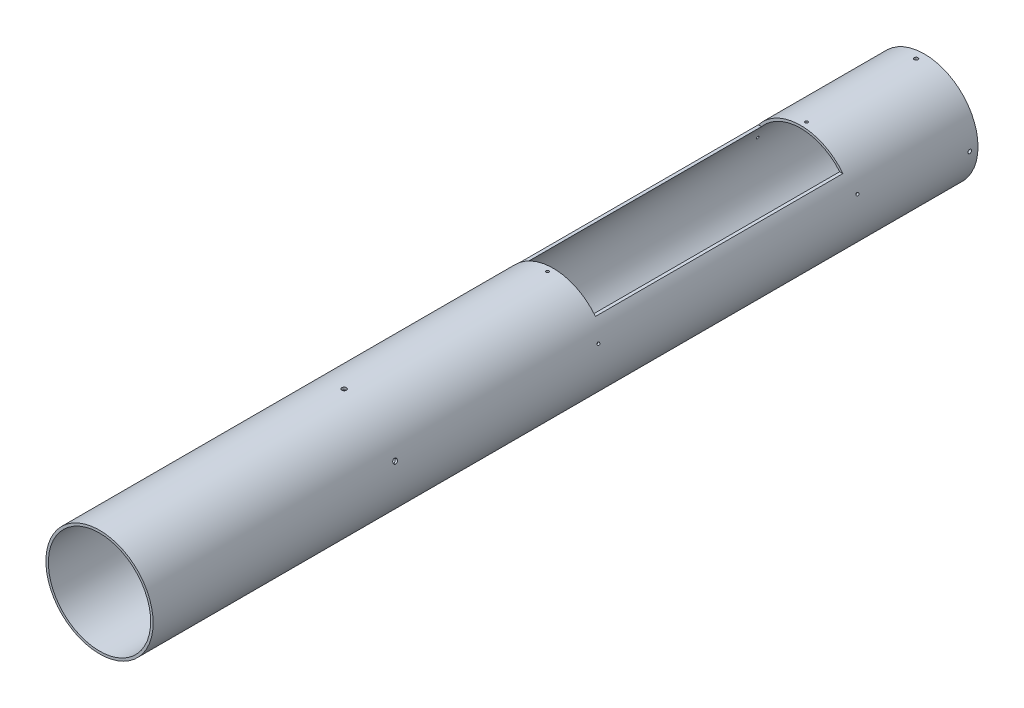
SolidWorks part; units mm, degrees
note: '?' marks a value the reader was unsure of.
material "Thornel Mat VMA"
ref_plane "Front Plane" through (0, 0, 0) normal (0, 0, 1) x (1, 0, 0)
ref_plane "Top Plane" through (0, 0, 0) normal (0, 1, 0) x (1, 0, 0)
ref_plane "Right Plane" through (0, 0, 0) normal (1, 0, 0) x (0, 0, -1)
sketch "Sketch1" plane through (0, 0, 0) normal (0, 0, 1) x (1, 0, 0)
  circle A0 centre (0, 0) radius 62
  circle A1 centre (0, 0) radius 65
  dimension "D1" = 124
  dimension "D2" = 3
extrude "Boss-Extrude1" add sketch "Sketch1" along normal blind 1000
ref_axis "Axis1" through (0, 0, 1000) along (0, 0, -1)?
sketch "Sketch2" plane through (0, 0, 0) normal (0, 1, 0) x (1, 0, 0)
  line L0 (62, 0) -> (-62, 0) construction
  circle A0 centre (0, -224) radius 1
  circle A1 centre (0, -184) radius 1
  dimension "D1" = 2
  dimension "D3" = 2
  dimension "D2" = 224
  dimension "D4" = 40
ref_plane "Plane1" through (0, 0, 0) normal (-0.7071, 0.7071, 0) x (0.7071, 0.7071, 0)
ref_plane "Plane2" through (0, 40, 0) normal (0, 1, 0) x (1, 0, 0)
sketch "Sketch4" plane through (0, 40, 0) normal (0, 1, 0) x (1, 0, 0)
  line L0 (-65, 0) -> (-65, -1000) construction
  line L1 (-65, -150) -> (65, -150)
  line L2 (-65, -150) -> (-65, -450)
  line L3 (-65, -450) -> (65, -450)
  line L4 (65, -150) -> (65, -450)
  line L5 (65, -1000) -> (65, 0) construction
  line L6 (65, 0) -> (-65, 0) construction
  dimension "D1" = 150
  dimension "D2" = 300
extrude "Cut-Extrude4" cut sketch "Sketch4" along normal blind 516
hole_wizard "M4 Clearance Hole2" positions "3DSketch2" profile "Sketch18" hole size "M4" standard "ISO" end condition up to next
sketch3d "3DSketch2"
  line L0 (0, 0, 1000) -> (0, 0, 0) construction
  circle A0 centre (0, 0, 10) radius 65
  circle A2 centre (0, 0, 1000) radius 65 construction
  circle A3 centre (0, 0, 0) radius 65 construction
  point P0 (0, 65, 10)
  point P2 (65, 0, 10)
  point P4 (0, -65, 10)
  point P6 (-65, 0, 10)
  point P11 (0, 0, 75)
  point P19 (0, 0, 1065)
  point P22 (0, 0, 65)
  dimension "D1" = 10
sketch "Sketch18" plane through (0, 65, 10) normal (1, 0, 0) x (0, 0, 1)
  line L0 (0, 0) -> (0, 3)
  line L1 (0, 3) -> (2.25, 3)
  line L2 (2.25, 3) -> (2.25, 0)
  line L5 (2.25, 0) -> (0, 0)
  line L11 (0, -6.35) -> (0, 107.95) construction
  dimension "Thru Hole Dia." = 4.5
  dimension "Thru Hole Depth" = 3
hole_wizard "M3 Clearance Hole1" positions "3DSketch3" profile "Sketch19" hole size "M3" standard "ISO"
sketch3d "3DSketch3"
  line L0 (-61.8187, 20.0861, 143) -> (0, 65, 143) construction
  line L1 (0, 65, 143) -> (61.8187, 20.0861, 143) construction
  line L2 (61.8187, 20.0861, 143) -> (38.206, -52.5861, 143) construction
  line L3 (38.206, -52.5861, 143) -> (-38.206, -52.5861, 143) construction
  line L4 (-38.206, -52.5861, 143) -> (-61.8187, 20.0861, 143) construction
  line L5 (-38.206, -52.5861, 457) -> (-61.8187, 20.0861, 457) construction
  line L6 (38.206, -52.5861, 457) -> (-38.206, -52.5861, 457) construction
  line L7 (61.8187, 20.0861, 457) -> (38.206, -52.5861, 457) construction
  line L8 (0, 65, 457) -> (61.8187, 20.0861, 457) construction
  line L9 (-61.8187, 20.0861, 457) -> (0, 65, 457) construction
  line L10 (0, 0, 1000) -> (0, 0, 0) construction
  line L11 (0, 65, 703.5) -> (61.8187, 20.0861, 703.5) construction
  line L12 (61.8187, 20.0861, 703.5) -> (38.206, -52.5861, 703.5) construction
  line L13 (38.206, -52.5861, 703.5) -> (-38.206, -52.5861, 703.5) construction
  line L14 (-38.206, -52.5861, 703.5) -> (-61.8187, 20.0861, 703.5) construction
  line L15 (-61.8187, 20.0861, 703.5) -> (0, 65, 703.5) construction
  circle A0 centre (0, 0, 143) radius 65 construction
  circle A1 centre (0, 0, 1000) radius 65 construction
  circle A3 centre (0, 0, 457) radius 65 construction
  circle A4 centre (0, 0, 0) radius 65 construction
  circle A5 centre (0, 0, 703.5) radius 65 construction
  point P0 (0, 65, 143)
  point P3 (0, 0, 208)
  point P8 (0, 0, 1065)
  point P15 (61.8187, 20.0861, 143)
  point P24 (61.8187, 20.0861, 143)
  point P26 (61.8187, 20.0861, 143)
  point P28 (38.206, -52.5861, 143)
  point P30 (-38.206, -52.5861, 143)
  point P32 (-61.8187, 20.0861, 143)
  point P44 (0, 0, 392)
  point P45 (-38.206, -52.5861, 457)
  point P52 (0, 0, 65)
  point P75 (0, 65, 457)
  point P77 (-61.8187, 20.0861, 457)
  point P81 (-38.206, -52.5861, 457)
  point P83 (-38.206, -52.5861, 457)
  point P85 (38.206, -52.5861, 457)
  point P87 (61.8187, 20.0861, 457)
  point P95 (-61.8187, 20.0861, 457)
  point P97 (-38.206, -52.5861, 457)
  point P104 (0, 0, 638.5)
  point P110 (0, 65, 703.5)
  point P111 (-61.8187, 20.0861, 703.5)
  point P112 (-38.206, -52.5861, 703.5)
  point P113 (-38.206, -52.5861, 703.5)
  point P114 (38.206, -52.5861, 703.5)
  point P115 (61.8187, 20.0861, 703.5)
  point P116 (-61.8187, 20.0861, 703.5)
  point P117 (-38.206, -52.5861, 703.5)
  dimension "D1" = 7
  dimension "D3" = 296.5
  dimension "D2" = 7
sketch "Sketch19" plane through (0, 65, 143) normal (1, 0, 0) x (0, 0, 1)
  line L0 (0, 0) -> (0, 3)
  line L1 (0, 3) -> (1.7, 3)
  line L2 (1.7, 3) -> (1.7, 0)
  line L5 (1.7, 0) -> (0, 0)
  line L11 (0, -6.35) -> (0, 107.95) construction
  dimension "Thru Hole Dia." = 3.4
  dimension "Thru Hole Depth" = 3
hole_wizard "M5 Clearance Hole1" positions "3DSketch4" profile "Sketch20" hole size "M5" standard "ISO"
sketch3d "3DSketch4"
  point P0 (-61.8187, 20.0861, 703.5)
  point P2 (-38.206, -52.5861, 703.5)
  point P4 (38.206, -52.5861, 703.5)
  point P6 (61.8187, 20.0861, 703.5)
  point P8 (0, 65, 703.5)
sketch "Sketch20" plane through (-61.8187, 20.0861, 703.5) normal (0, 0, 1) x (-0.309, -0.9511, 0)
  line L0 (0, 0) -> (0, 3)
  line L1 (0, 3) -> (2.75, 3)
  line L2 (2.75, 3) -> (2.75, 0)
  line L5 (2.75, 0) -> (0, 0)
  line L11 (0, -6.35) -> (0, 107.95) construction
  dimension "Thru Hole Dia." = 5.5
  dimension "Thru Hole Depth" = 3
ref_plane "Plane3" through (0, 0, 135) normal (0, 0, 1) x (1, 0, 0)
sketch "Sketch9" plane through (0, 0, 135) normal (0, 0, 1) x (1, 0, 0)
  line L0 (-37.2825, -53.2449) -> (37.2825, -53.2449) construction
  line L3 (0, 0) -> (-37.2825, -53.2449)
  line L4 (1, 0) -> (-1, 0) construction
  line L5 (0, 0) -> (37.2825, -53.2449)
  arc A0 (-37.2825, -53.2449) -> (37.2825, -53.2449) centre (0, 0) ccw
  circle A1 centre (0, 0) radius 65 construction
  circle A2 centre (0, 0) radius 65 construction
  point P6 (0, 0)
  dimension "D1" = 70
  dimension "D2" = 110
extrude "Cut-Extrude8" cut sketch "Sketch9" against normal blind 103
